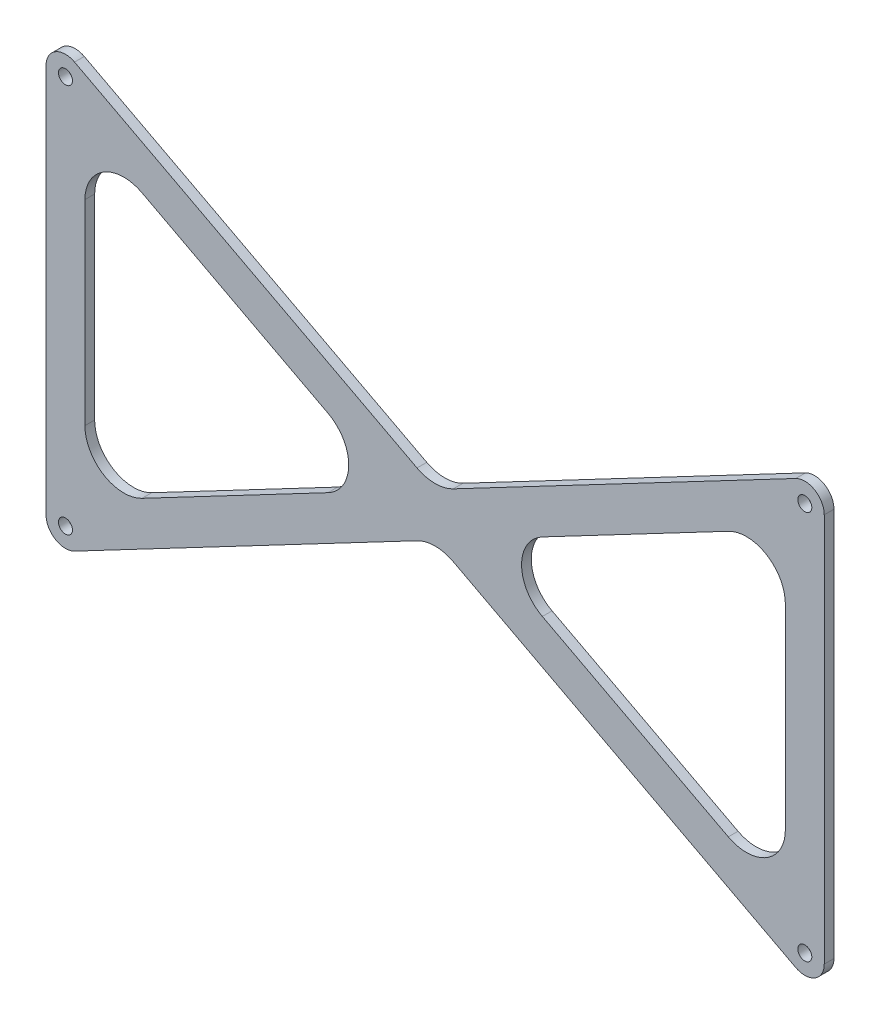
SolidWorks part; units mm, degrees
ref_plane "Front Plane" through (0, 0, 0) normal (0, 0, 1) x (1, 0, 0)
ref_plane "Top Plane" through (0, 0, 0) normal (0, 1, 0) x (1, 0, 0)
ref_plane "Right Plane" through (0, 0, 0) normal (1, 0, 0) x (0, 0, -1)
sketch "Sketch1" plane through (0, 0, 0) normal (0, 0, 1) x (1, 0, 0)
  line L0 (-120.65, -63.5) -> (120.65, 63.5) construction
  line L3 (-114.3, -52.9821) -> (-13.634, 0)
  line L10 (-117.6925, -69.1192) -> (0, -7.1758)
  line L11 (-120.65, 63.5) -> (120.65, -63.5) construction
  line L12 (-117.6925, 69.1192) -> (0, 7.1758)
  line L13 (-114.3, 52.9821) -> (-13.634, 0)
  line L14 (0, 7.1758) -> (117.6925, 69.1192)
  line L15 (0, -7.1758) -> (117.6925, -69.1192)
  line L16 (13.634, 0) -> (114.3, 52.9821)
  line L17 (13.634, 0) -> (114.3, -52.9821)
  line L18 (-127, 63.5) -> (-127, -63.5)
  line L19 (-114.3, 52.9821) -> (-114.3, -52.9821)
  line L20 (127, 63.5) -> (127, -63.5)
  line L21 (114.3, 52.9821) -> (114.3, -52.9821)
  arc A4 (-127, -63.5) -> (-117.6925, -69.1192) centre (-120.65, -63.5) ccw
  arc A5 (127, 63.5) -> (117.6925, 69.1192) centre (120.65, 63.5) ccw
  arc A6 (-117.6925, 69.1192) -> (-127, 63.5) centre (-120.65, 63.5) ccw
  arc A7 (117.6925, -69.1192) -> (127, -63.5) centre (120.65, -63.5) ccw
  point P2 (0, 0)
  point P9 (0, 0)
  point P13 (0, 0)
  point P22 (114.3, 76.3334)
  point P25 (114.3, -76.3334)
  point P26 (0, 0)
  dimension "D1" = 254
  dimension "D3" = 6.35
  dimension "D2" = 127
extrude "Boss-Extrude1" add sketch "Sketch1" along normal blind 3.175
sketch "Sketch2" plane through (0, 0, 3.175) normal (0, 0, 1) x (1, 0, 0)
  circle A0 centre (-120.65, 63.5) radius 2.286
  circle A1 centre (-120.65, -63.5) radius 2.286
  circle A2 centre (120.65, -63.5) radius 2.286
  circle A3 centre (120.65, 63.5) radius 2.286
  arc A4 (-117.6925, 69.1192) -> (-127, 63.5) centre (-120.65, 63.5) ccw construction
  arc A5 (-127, -63.5) -> (-117.6925, -69.1192) centre (-120.65, -63.5) ccw construction
  arc A6 (117.6925, -69.1192) -> (127, -63.5) centre (120.65, -63.5) ccw construction
  arc A7 (127, 63.5) -> (117.6925, 69.1192) centre (120.65, 63.5) ccw construction
  dimension "D1" = 4.572
extrude "Cut-Extrude1" cut sketch "Sketch2" against normal through all
fillet "Fillet1" radius 12.7 8 edges at (114.3, -52.9821, 1.5875) (114.3, 52.9821, 1.5875) (13.634, 0, 1.5875) (-114.3, -52.9821, 1.5875) (-13.634, 0, 1.5875) (-114.3, 52.9821, 1.5875) (0, 7.1758, 1.5875) (0, -7.1758, 1.5875)
